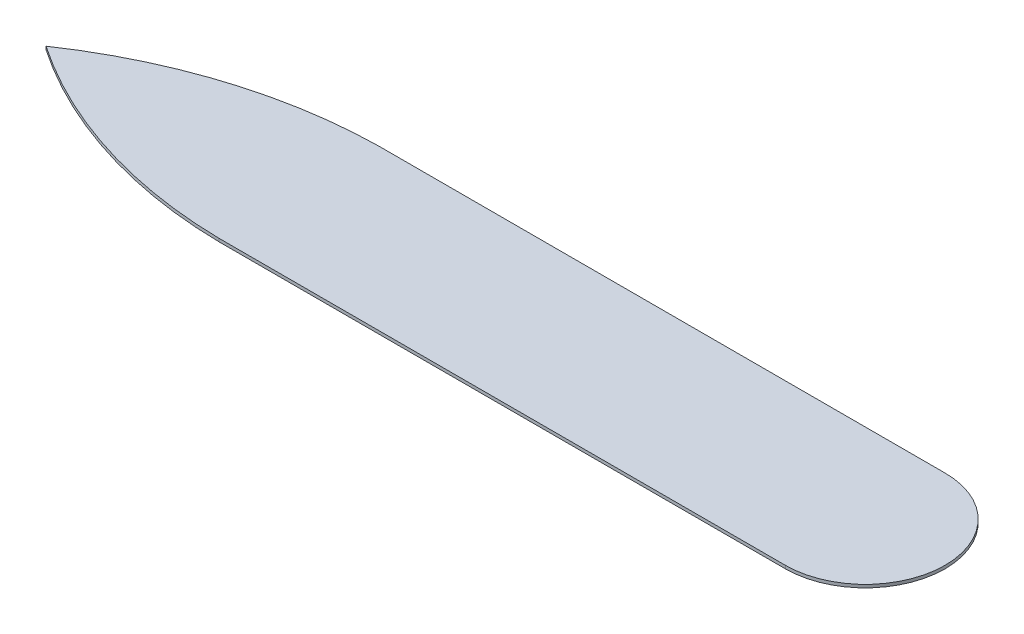
SolidWorks part; units mm, degrees
ref_plane "Front Plane" through (0, 0, 0) normal (0, 0, 1) x (1, 0, 0)
ref_plane "Top Plane" through (0, 0, 0) normal (0, 1, 0) x (1, 0, 0)
ref_plane "Right Plane" through (0, 0, 0) normal (1, 0, 0) x (0, 0, -1)
sketch "Sketch1" plane through (0, 0, 0) normal (0, 1, 0) x (1, 0, 0)
  line L0 (800, 78) -> (0, 78) construction
  line L1 (247.0699, 0) -> (800, 0)
  line L2 (0, 0) -> (0, 156) construction
  line L3 (247.0699, 156) -> (800, 156)
  arc A0 (800, 156) -> (800, 0) centre (800, 78) cw
  arc A1 (247.0699, 156) -> (0, 78) centre (253.6132, -295.0311) ccw
  arc A2 (247.0699, 0) -> (0, 78) centre (253.6132, 451.0311) cw
  point P6 (0, 0)
  point P12 (26.6897, 78)
  point P13 (0, 0)
  point P14 (0, 0)
  point P15 (0, 0)
  dimension "D1" = 800
  dimension "D2" = 156
  dimension "D3" = 247.0699
extrude "Boss-Extrude1" add sketch "Sketch1" along normal blind 3
